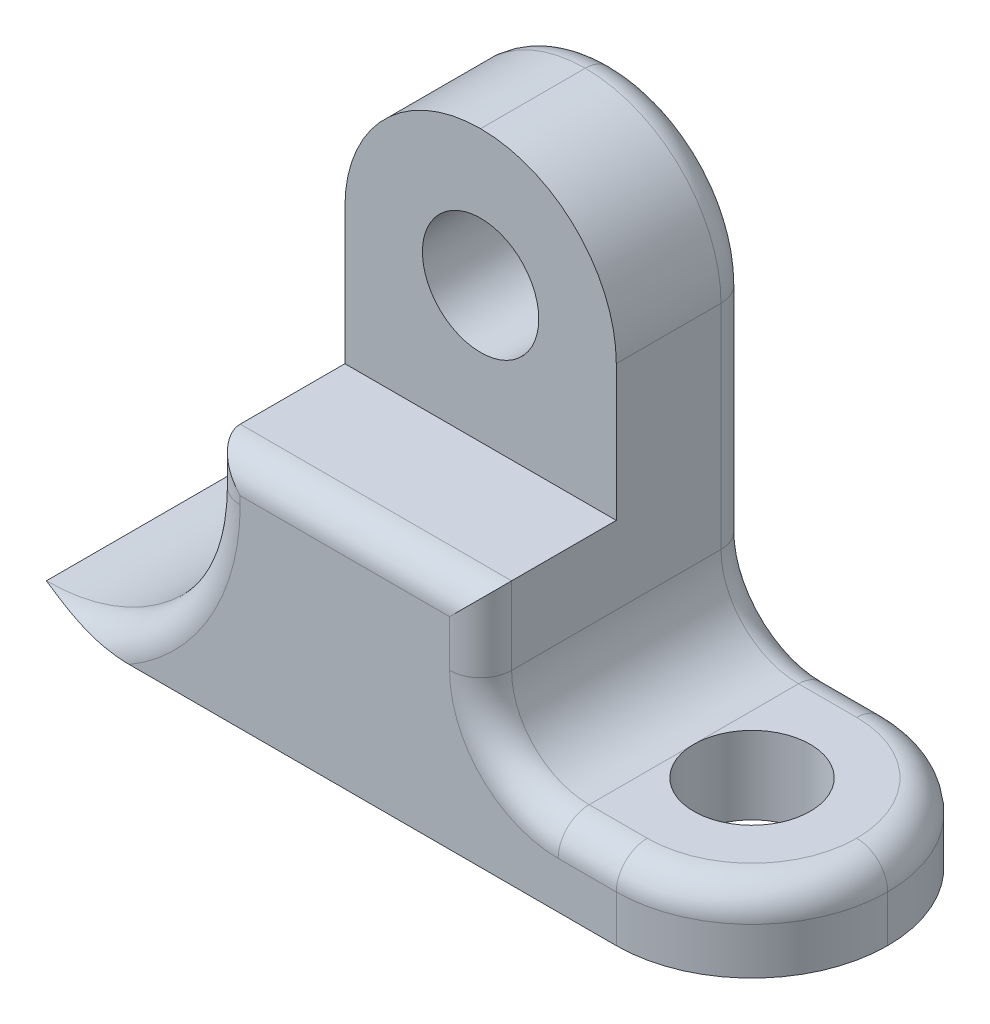
SolidWorks part; units mm, degrees
ref_plane "前视基准面" through (0, 0, 0) normal (0, 0, 1) x (1, 0, 0)
ref_plane "上视基准面" through (0, 0, 0) normal (0, 1, 0) x (1, 0, 0)
ref_plane "右视基准面" through (0, 0, 0) normal (1, 0, 0) x (0, 0, -1)
sketch "草图1" plane through (0, 0, 0) normal (0, 0, 1) x (1, 0, 0)
  line L0 (3.5, -6.5) -> (10.5, -6.5)
  line L1 (-3.5, 6.5) -> (3.5, 6.5)
  line L2 (-3.5, 6.5) -> (-3.5, -6.5)
  line L3 (-3.5, -6.5) -> (3.5, -6.5)
  line L4 (3.5, 6.5) -> (3.5, -6.5)
  line L5 (-3.5, 6.5) -> (3.5, -6.5) construction
  line L6 (-3.5, -6.5) -> (3.5, 6.5) construction
  line L7 (10.5, -6.5) -> (10.5, -4.5)
  line L8 (10.5, -4.5) -> (3.5, -4.5)
  line L9 (-3.5, -6.5) -> (-8.5, -6.5)
  arc A0 (-8.5, -6.5) -> (-3.5, -1.5) centre (-8.5, -1.5) ccw
  point P0 (0, 0)
  dimension "D1" = 7
  dimension "D2" = 13
  dimension "D3" = 7
  dimension "D4" = 2
  dimension "D5" = 5
extrude "凸台-拉伸1" add sketch "草图1" along normal blind 7 contours A0 L9 L2 | L4 L1 L2 L3 | L7 L8 L4 L0 region at (7, -5.5, 0) region at (0, 0, 0) region at (-4.6168, -5.3832, 0)
sketch "草图2" plane through (0, 0, 7) normal (0, 0, 1) x (1, 0, 0)
  line L0 (-3.5, 6.5) -> (3.5, 6.5)
  line L1 (3.5, 6.5) -> (3.5, -0.5)
  line L2 (3.5, 6.5) -> (3.5, -4.5) construction
  line L3 (3.5, -0.5) -> (-3.5, -0.5)
  line L4 (-3.5, 6.5) -> (-3.5, -1.5) construction
  line L5 (-3.5, -0.5) -> (-3.5, 6.5)
  dimension "D1" = 7
extrude "切除-拉伸1" cut sketch "草图2" against normal blind 3.5
fillet "圆角1" radius 3.5 4 edges at (10.5, -5.5, 0) (10.5, -5.5, 7) (3.5, 6.5, 1.75) (-3.5, 6.5, 1.75)
sketch "草图3" plane through (0, 0, 3.5) normal (0, 0, 1) x (1, 0, 0)
  circle A0 centre (0, 3) radius 1.5
  dimension "D1" = 3
extrude "切除-拉伸2" cut sketch "草图3" against normal through all
sketch "草图4" plane through (0, -4.5, 0) normal (0, 1, 0) x (1, 0, 0)
  circle A0 centre (7, -3.5) radius 1.5
  dimension "D1" = 3
extrude "切除-拉伸3" cut sketch "草图4" against normal through all
fillet "圆角2" radius 2 1 edges at (3.5, -4.5, 3.5)
fillet "圆角3" radius 0.8 15 edges at (-3.5, -1, 7) (-4.9645, -5.0355, 0) (-3.5, 0.75, 0) (-2.4749, 5.4749, 0) (2.4749, 5.4749, 0) (3.5, 0.25, 0) (3.5, -1.5, 7) (4.0858, -3.9142, 7) (6.25, -4.5, 7) (9.4749, -4.5, 5.9749) (9.4749, -4.5, 1.0251) (6.25, -4.5, 0) (0, -0.5, 7) (-4.9645, -5.0355, 7) (4.0858, -3.9142, 0)
